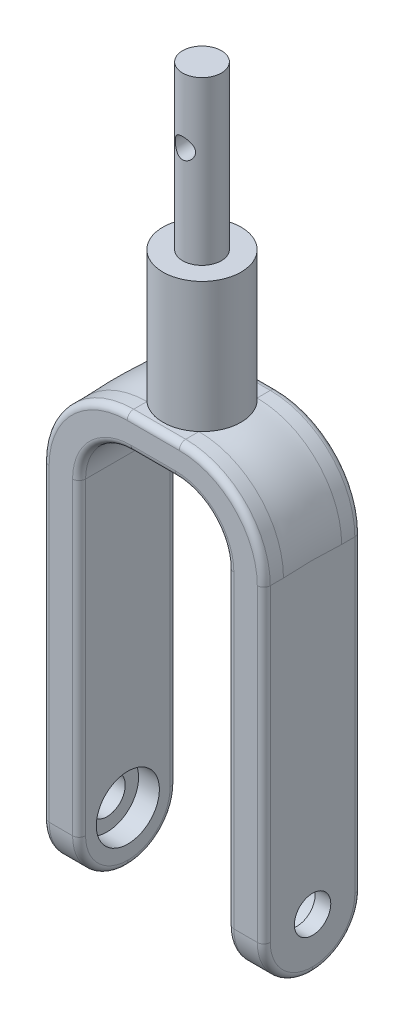
SolidWorks part; units mm, degrees
ref_plane "前视基准面" through (0, 0, 0) normal (0, 0, 1) x (1, 0, 0)
ref_plane "上视基准面" through (0, 0, 0) normal (0, 1, 0) x (1, 0, 0)
ref_plane "右视基准面" through (0, 0, 0) normal (1, 0, 0) x (0, 0, -1)
sketch "草图1" plane through (0, 0, 0) normal (0, 1, 0) x (1, 0, 0)
  line L1 (17, 7.5) -> (-17, 7.5)
  line L2 (17, 7.5) -> (17, -7.5)
  line L3 (17, -7.5) -> (-17, -7.5)
  line L4 (-17, 7.5) -> (-17, -7.5)
  line L5 (17, 7.5) -> (-17, -7.5) construction
  line L6 (17, -7.5) -> (-17, 7.5) construction
  point P0 (0, 0)
extrude "凸台-拉伸1" add sketch "草图1" against normal blind 68
sketch "草图2" plane through (0, 0, 0) normal (0, 1, 0) x (1, 0, 0)
  circle A0 centre (0, 0) radius 6
extrude "凸台-拉伸2" add sketch "草图2" along normal blind 20
sketch "草图7" plane through (0, 20, 0) normal (0, 1, 0) x (1, 0, 0)
  circle A0 centre (0, 0) radius 2.98
extrude "凸台-拉伸3" add sketch "草图7" along normal blind 25
sketch "草图8" plane through (0, 0, 0) normal (0, 0, 1) x (1, 0, 0)
  line L0 (0, 20) -> (0, 35) construction
  line L1 (6, 20) -> (-6, 20) construction
  circle A1 centre (0, 35) radius 1.55
extrude "切除-拉伸5" cut sketch "草图8" against normal through all both and the other way through all
sketch "草图3" plane through (0, 0, 7.5) normal (0, 0, 1) x (1, 0, 0)
  line L0 (-17, -68) -> (17, -68) construction
  line L1 (-11.4, -68) -> (11.4, -68)
  line L2 (-11.4, -68) -> (-11.4, -5)
  line L3 (-11.4, -5) -> (11.4, -5)
  line L4 (11.4, -68) -> (11.4, -5)
extrude "切除-拉伸1" cut sketch "草图3" against normal through all
fillet "圆角1" radius 8 2 edges at (11.4, -5, 0) (-11.4, -5, 0)
fillet "圆角5" radius 13 2 edges at (17, 0, 0) (-17, 0, 0)
fillet "圆角3" radius 7.5 4 edges at (14.2, -68, -7.5) (14.2, -68, 7.5) (-14.2, -68, -7.5) (-14.2, -68, 7.5)
fillet "圆角2" radius 1 28 edges at (-17, -36.75, -7.5) (0, 0, -7.5) (17, -36.75, -7.5) (17, -36.75, 7.5) (0, 0, 7.5) (-17, -36.75, 7.5) (-9.0569, -7.3431, 7.5) (0, -5, 7.5) (9.0569, -7.3431, 7.5) (11.4, -36.75, 7.5) (11.4, -36.75, -7.5) (9.0569, -7.3431, -7.5) (0, -5, -7.5) (-9.0569, -7.3431, -7.5) (-11.4, -36.75, -7.5) (-11.4, -36.75, 7.5) (11.4, -65.8033, 5.3033) (11.4, -65.8033, -5.3033) (-11.4, -65.8033, -5.3033) (-11.4, -65.8033, 5.3033) (-17, -65.8033, 5.3033) (-17, -65.8033, -5.3033) (17, -65.8033, -5.3033) (17, -65.8033, 5.3033) (-13.1924, -3.8076, -7.5) (13.1924, -3.8076, -7.5) (13.1924, -3.8076, 7.5) (-13.1924, -3.8076, 7.5)
sketch "草图4" plane through (17, 0, 0) normal (1, 0, 0) x (0, 0, -1)
  circle A0 centre (0, -60) radius 2.8
extrude "切除-拉伸2" cut sketch "草图4" against normal through all
sketch "草图6" plane through (11.4, 0, 0) normal (1, 0, 0) x (0, 0, -1)
  circle A0 centre (0, -60) radius 4.85
extrude "切除-拉伸4" cut sketch "草图6" along normal blind 3.2
mirror "镜向1" about plane through (0, 0, 0) normal (1, 0, 0) of "切除-拉伸4"
